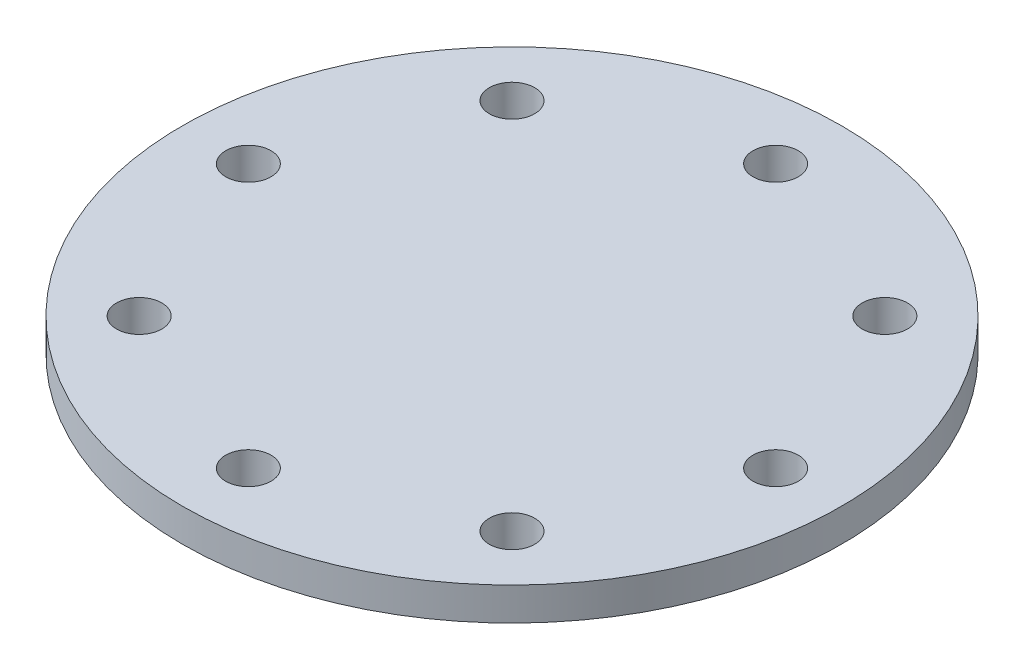
SolidWorks part; units mm, degrees
ref_plane "Front Plane" through (0, 0, 0) normal (0, 0, 1) x (1, 0, 0)
ref_plane "Top Plane" through (0, 0, 0) normal (0, 1, 0) x (1, 0, 0)
ref_plane "Right Plane" through (0, 0, 0) normal (1, 0, 0) x (0, 0, -1)
sketch "Sketch2" plane through (0, 0, 0) normal (0, 1, 0) x (1, 0, 0)
  circle A0 centre (0, 0) radius 127
  dimension "D1" = 254
extrude "Extrude1" add sketch "Sketch2" along normal blind 12.7
hole_wizard "11/16 (0.6875) Diameter Hole1" positions "Sketch6" profile "Sketch5" hole size "11/16" standard "Ansi Inch" end condition through all
sketch "Sketch6" plane through (0, 12.7, 0) normal (0, 1, 0) x (-1, 0, 0)
  point P0 (-101.6, 0)
  dimension "D1" = 101.6
sketch "Sketch5" plane through (101.6, 12.7, 0) normal (1, 0, 0) x (0, 0, 1)
  line L0 (0, 0) -> (0, 12.7)
  line L1 (0, 12.7) -> (8.7312, 12.7)
  line L2 (8.7312, 12.7) -> (8.7312, 0)
  line L5 (8.7312, 0) -> (0, 0)
  line L11 (0, -6.35) -> (0, 107.95) construction
  dimension "Thru Hole Dia." = 17.4625
  dimension "Thru Hole Depth" = 12.7
ref_axis "Axis1" through (0, 12.7, 0) along (0, -1, 0)
pattern_circular "CirPattern1" count 8 over 360 about axis through (0, 12.7, 0) along (0, -1, 0) of "11/16 (0.6875) Diameter Hole1"
